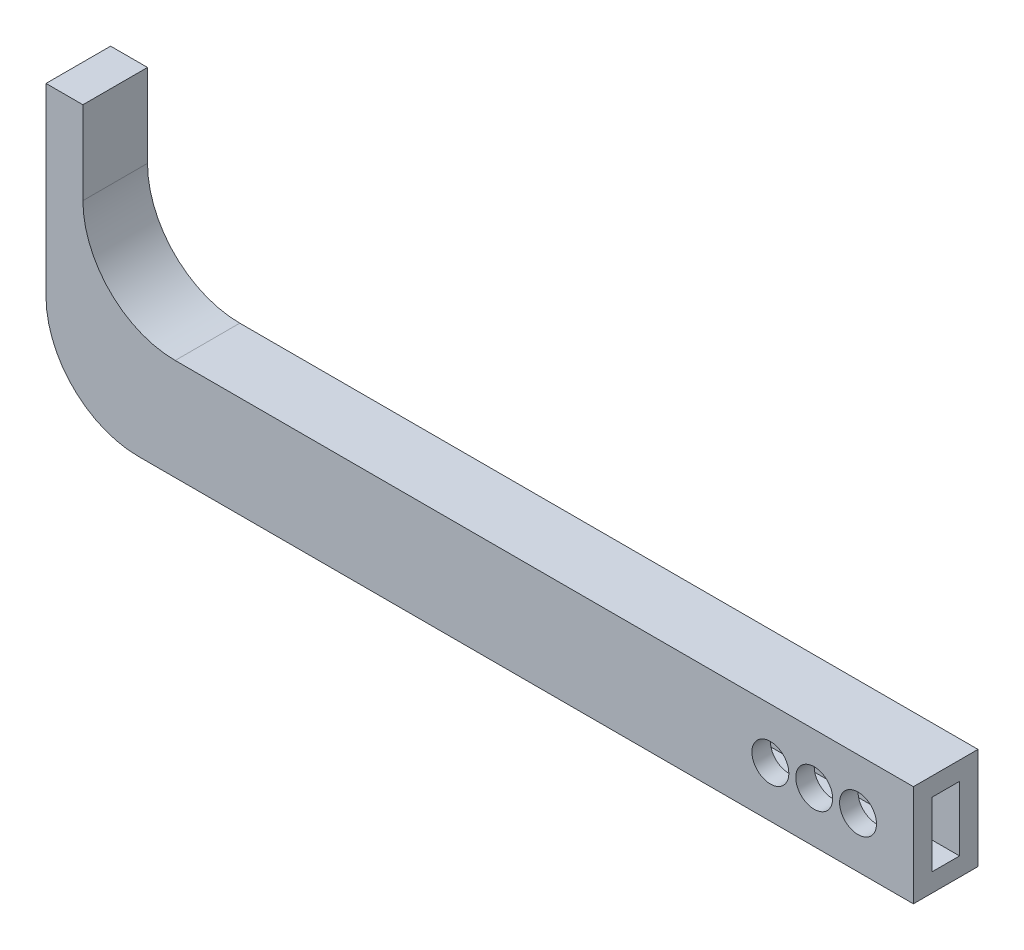
SolidWorks part; units mm, degrees
ref_plane "Plan de face" through (0, 0, 0) normal (0, 0, 1) x (1, 0, 0)
ref_plane "Plan de dessus" through (0, 0, 0) normal (0, 1, 0) x (1, 0, 0)
ref_plane "Plan de droite" through (0, 0, 0) normal (1, 0, 0) x (0, 0, -1)
sketch "Sketch1" plane through (0, 0, 0) normal (0, 0, 1) x (1, 0, 0)
  line L0 (0, 0) -> (-47, 0)
  line L1 (-47, 0) -> (-47, 15)
  line L2 (-47, 15) -> (-45, 15)
  line L3 (-45, 15) -> (-45, 5.5)
  line L4 (-45, 5.5) -> (0, 5.5)
  line L5 (0, 5.5) -> (0, 0)
  dimension "D1" = 45
  dimension "D2" = 2
  dimension "D3" = 15
  dimension "D4" = 5.5
extrude "Boss-Extrude1" add sketch "Sketch1" along normal blind 3.5
fillet "Fillet2" radius 5 2 edges at (-47, 0, 1.75) (-45, 5.5, 1.75)
shell "Shell1" thickness 1 removed face at (0, 2.75, 1.75)
sketch "Sketch2" plane through (0, 0, 3.5) normal (0, 0, 1) x (1, 0, 0)
  line L0 (0, 0) -> (0, 5.5) construction
  line L1 (0, 5.5) -> (-40, 5.5) construction
  circle A0 centre (-3, 2.75) radius 1
  circle A1 centre (-5.375, 2.75) radius 1
  circle A2 centre (-7.75, 2.75) radius 1
  dimension "D1" = 2
  dimension "D2" = 2
  dimension "D3" = 2
  dimension "D4" = 4.75
  dimension "D5" = 2.375
  dimension "D6" = 3
  dimension "D7" = 2.75
  dimension "D8" = 2.75
  dimension "D9" = 2.75
extrude "Cut-Extrude1" cut sketch "Sketch2" against normal up to surface (3.5 mm away) up to face at (-33.5089, 6.8036, 0)
